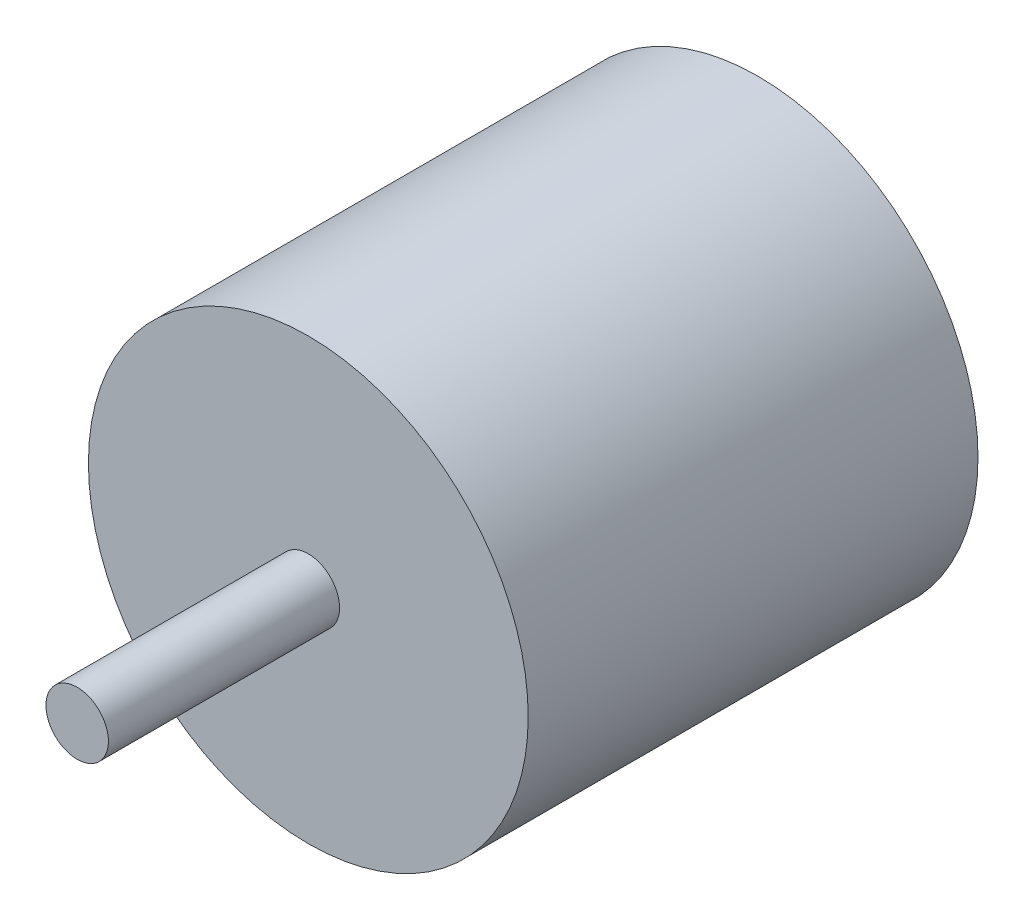
SolidWorks part; units mm, degrees
ref_plane "Front Plane" through (0, 0, 0) normal (0, 0, 1) x (1, 0, 0)
ref_plane "Top Plane" through (0, 0, 0) normal (0, 1, 0) x (1, 0, 0)
ref_plane "Right Plane" through (0, 0, 0) normal (1, 0, 0) x (0, 0, -1)
sketch "Эскиз1" plane through (0, 0, 0) normal (0, 0, 1) x (1, 0, 0)
  circle A0 centre (0, 0) radius 17.6
  circle A2 centre (0, 0) radius 2.5
  dimension "D1" = 35.2
  dimension "D2" = 5
extrude "Бобышка-Вытянуть1" add sketch "Эскиз1" along normal blind 36 contours A0 A2 | A2 region at (-17.1022, 0, 0) region at (0, 0, 0)
extrude "Бобышка-Вытянуть2" add sketch "Эскиз1<4>" against normal blind 2 contours A2 region at (0, 0, 0)
sketch "Эскиз1<4>" plane through (0, 0, 0) normal (0, 0, 1) x (1, 0, 0) same geometry as "Эскиз1"
extrude "Бобышка-Вытянуть3" add sketch "Эскиз1<5>" along normal blind 18.5 from surface contours A2 region at (0, 0, 0) starting at face at (17.6, 0, 36)
sketch "Эскиз1<5>" plane through (0, 0, 0) normal (0, 0, 1) x (1, 0, 0) same geometry as "Эскиз1"
sketch "Эскиз2" plane through (0, 0, 0) normal (0, 0, -1) x (-1, 0, 0)
  line L0 (0, 12.7296) -> (0, -13.7176) construction
  line L1 (-11.1336, 0) -> (11.8936, 0) construction
  circle A0 centre (0, 12.5) radius 1.5
  circle A1 centre (-9.5, 0) radius 1.5
  circle A2 centre (0, -12.5) radius 1.5
  circle A3 centre (9.5, 0) radius 1.5
  dimension "D1" = 3
  dimension "D3" = 9.5
  dimension "D2" = 12.5
extrude "Вырез-Вытянуть1" cut sketch "Эскиз2" against normal blind 3
